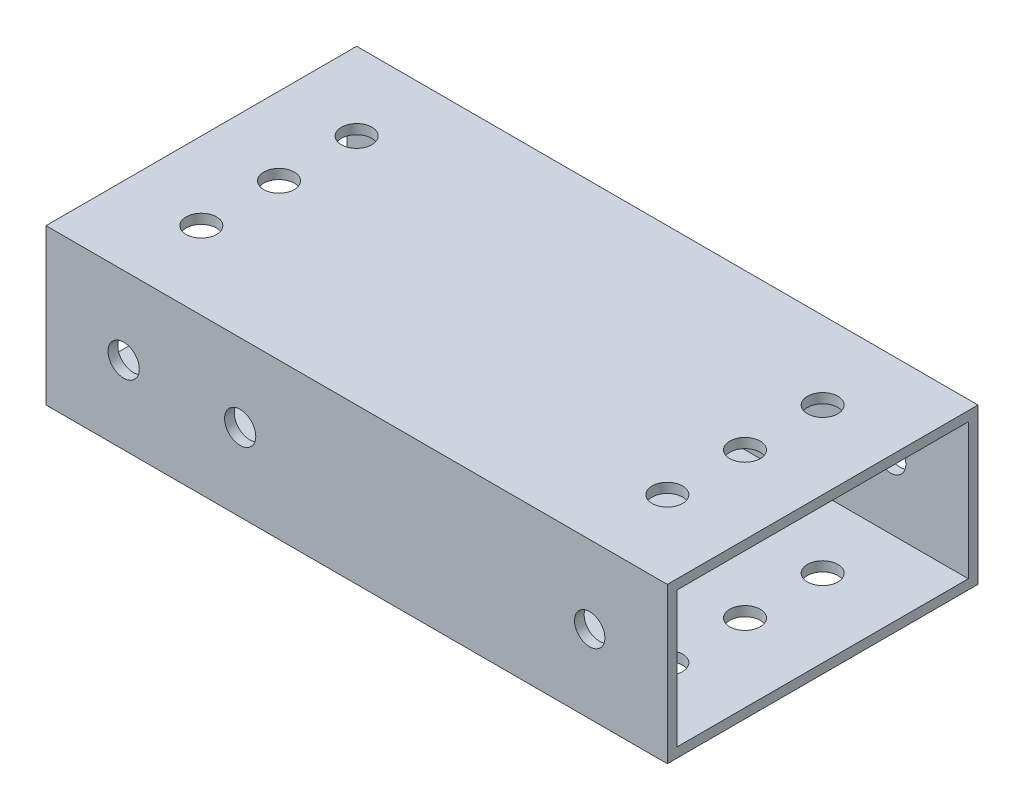
SolidWorks part; units mm, degrees
material "6061-T6 (SS)"
ref_plane "Front Plane" through (0, 0, 0) normal (0, 0, 1) x (1, 0, 0)
ref_plane "Top Plane" through (0, 0, 0) normal (0, 1, 0) x (1, 0, 0)
ref_plane "Right Plane" through (0, 0, 0) normal (1, 0, 0) x (0, 0, -1)
sketch "Sketch1" plane through (0, 0, 0) normal (1, 0, 0) x (0, 0, -1)
  line L1 (0, 0) -> (50.8, 0)
  line L2 (0, 0) -> (0, 25.4)
  line L3 (0, 25.4) -> (50.8, 25.4)
  line L4 (50.8, 0) -> (50.8, 25.4)
  dimension "D1" = 25.4
  dimension "D2" = 50.8
extrude "Boss-Extrude1" add sketch "Sketch1" along normal mid plane 101.6
shell "Shell1" thickness 1.5875 removed face at (-50.8, 12.7, -25.4) removed face at (50.8, 12.7, -25.4)
sketch "Sketch2" plane through (0, 25.4, 0) normal (0, 1, 0) x (1, 0, 0)
  line L0 (-38.1, 50.8) -> (-38.1, 0) construction
  line L1 (50.8, 50.8) -> (-50.8, 50.8) construction
  line L2 (50.8, 0) -> (-50.8, 0) construction
  line L3 (-50.8, 50.8) -> (-50.8, 0) construction
  circle A0 centre (-38.1, 25.4) radius 2.4892
  circle A1 centre (-38.1, 12.7) radius 2.4892
  circle A2 centre (-38.1, 38.1) radius 2.4892
  dimension "D1" = 4.9784
  dimension "D2" = 12.7
  dimension "D3" = 12.7
  dimension "D4" = 12.7
extrude "Cut-Extrude1" cut sketch "Sketch2" against normal through all
sketch "Sketch3" plane through (0, 0, 0) normal (0, 0, 1) x (1, 0, 0)
  line L0 (50.8, 25.4) -> (-50.8, 25.4) construction
  line L1 (-50.8, 25.4) -> (-50.8, 0) construction
  circle A0 centre (-38.1, 12.7) radius 2.4892
  dimension "D3" = 4.9784
  dimension "D1" = 12.7
  dimension "D2" = 12.7
extrude "Cut-Extrude2" cut sketch "Sketch3" against normal through all
mirror "Mirror1" about plane through (0, 0, 0) normal (1, 0, 0) of "Cut-Extrude2", "Cut-Extrude1"
sketch "Sketch4" plane through (0, 0, 0) normal (0, 0, 1) x (1, 0, 0)
  line L0 (-50.8, 25.4) -> (-50.8, 0) construction
  circle A0 centre (-19.05, 12.7) radius 2.5527
  circle A1 centre (-38.1, 12.7) radius 2.4892 construction
  point P5 (-50.8, 12.7)
  dimension "D1" = 19.05
  dimension "D2" = 5.1054
extrude "Cut-Extrude3" cut sketch "Sketch4" against normal through all
sketch "Sketch5" plane through (0, 0, 0) normal (0, 0, 1) x (1, 0, 0)
  circle A0 centre (-38.1, 12.7) radius 2.5527
  circle A1 centre (-19.05, 12.7) radius 2.5527 construction
extrude "Cut-Extrude4" cut sketch "Sketch5" against normal up to next
